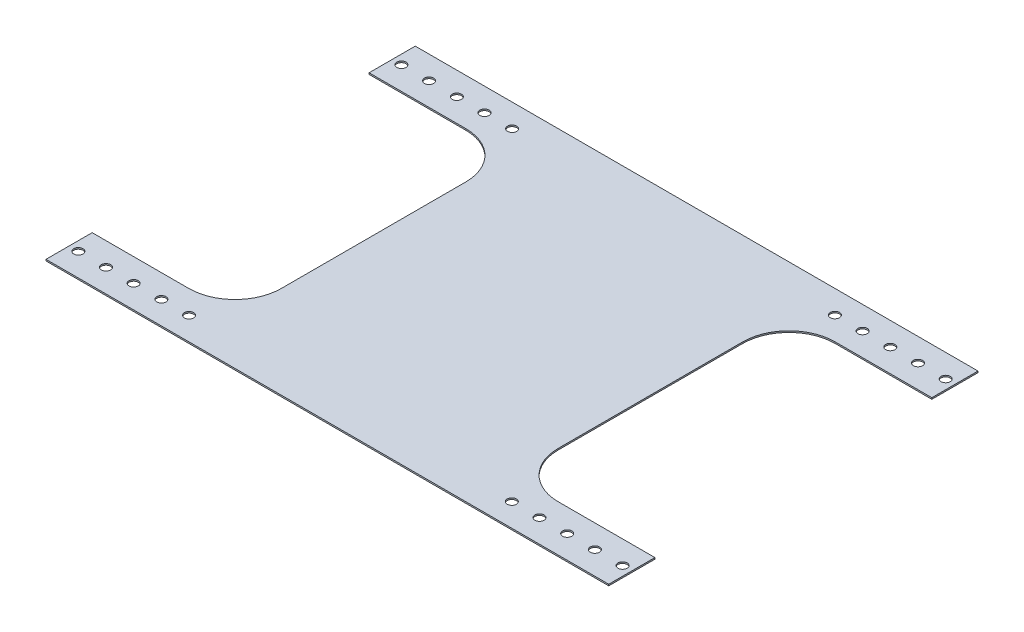
SolidWorks part; units mm, degrees
ref_plane "Front Plane" through (0, 0, 0) normal (0, 0, 1) x (1, 0, 0)
ref_plane "Top Plane" through (0, 0, 0) normal (0, 1, 0) x (1, 0, 0)
ref_plane "Right Plane" through (0, 0, 0) normal (1, 0, 0) x (0, 0, -1)
sketch "Sketch3" plane through (0, 0, 0) normal (0, 1, 0) x (1, 0, 0)
  line L0 (-152.4, 100) -> (152.4, 100)
  line L1 (-152.4, 100) -> (-152.4, 75)
  line L2 (-152.4, 75) -> (-100, 75)
  line L3 (-75, 50) -> (-75, -50)
  line L4 (0, 0) -> (-261.7187, 0) construction
  line L5 (0, 0) -> (0, 124.0234) construction
  line L6 (75, 50) -> (75, -50)
  line L7 (152.4, 75) -> (100, 75)
  line L8 (152.4, 100) -> (152.4, 75)
  line L9 (152.4, -100) -> (152.4, -75)
  line L10 (152.4, -75) -> (100, -75)
  line L11 (-152.4, -75) -> (-100, -75)
  line L12 (-152.4, -100) -> (-152.4, -75)
  line L13 (-152.4, -100) -> (152.4, -100)
  arc A0 (75, 50) -> (100, 75) centre (100, 50) cw
  arc A1 (100, -75) -> (75, -50) centre (100, -50) cw
  arc A2 (-100, -75) -> (-75, -50) centre (-100, -50) ccw
  arc A3 (-100, 75) -> (-75, 50) centre (-100, 50) cw
  point P13 (0, 100)
  point P16 (75, 0)
  point P17 (-75, 0)
  point P21 (75, 75)
  point P24 (75, -75)
  point P27 (-75, -75)
  point P30 (-75, 75)
  dimension "D5" = 25
  dimension "D1" = 25
  dimension "D3" = 200
  dimension "D4" = 150
  dimension "D2" = 304.8
extrude "Sheet" add sketch "Sketch3" along normal blind 0.7937
sketch "Sketch4" plane through (0, 0.7937, 0) normal (0, 1, 0) x (1, 0, 0)
  line L0 (-152.4, 87.5) -> (-75, 87.5) construction
  line L1 (-152.4, 100) -> (-152.4, 75) construction
  line L2 (-75, 50) -> (-75, -50) construction
  circle A0 centre (-147.4, 87.5) radius 2.5
  circle A1 centre (-132.4, 87.5) radius 2.5
  circle A2 centre (-117.4, 87.5) radius 2.5
  circle A3 centre (-102.4, 87.5) radius 2.5
  circle A4 centre (-87.4, 87.5) radius 2.5
  dimension "D1" = 5
  dimension "D2" = 5
  dimension "D4" = 15
  dimension "D3" = 5
extrude "MountHoles" cut sketch "Sketch4" against normal through all
mirror "Mirror3" about plane through (0, 0, 0) normal (0, 0, 1) of "MountHoles"
mirror "Mirror4" about plane through (0, 0, 0) normal (1, 0, 0) of "Mirror3"
equation "\"SheetLength\"=304.8"
equation "\"D2@Sketch3\"=\"SheetLength\""
